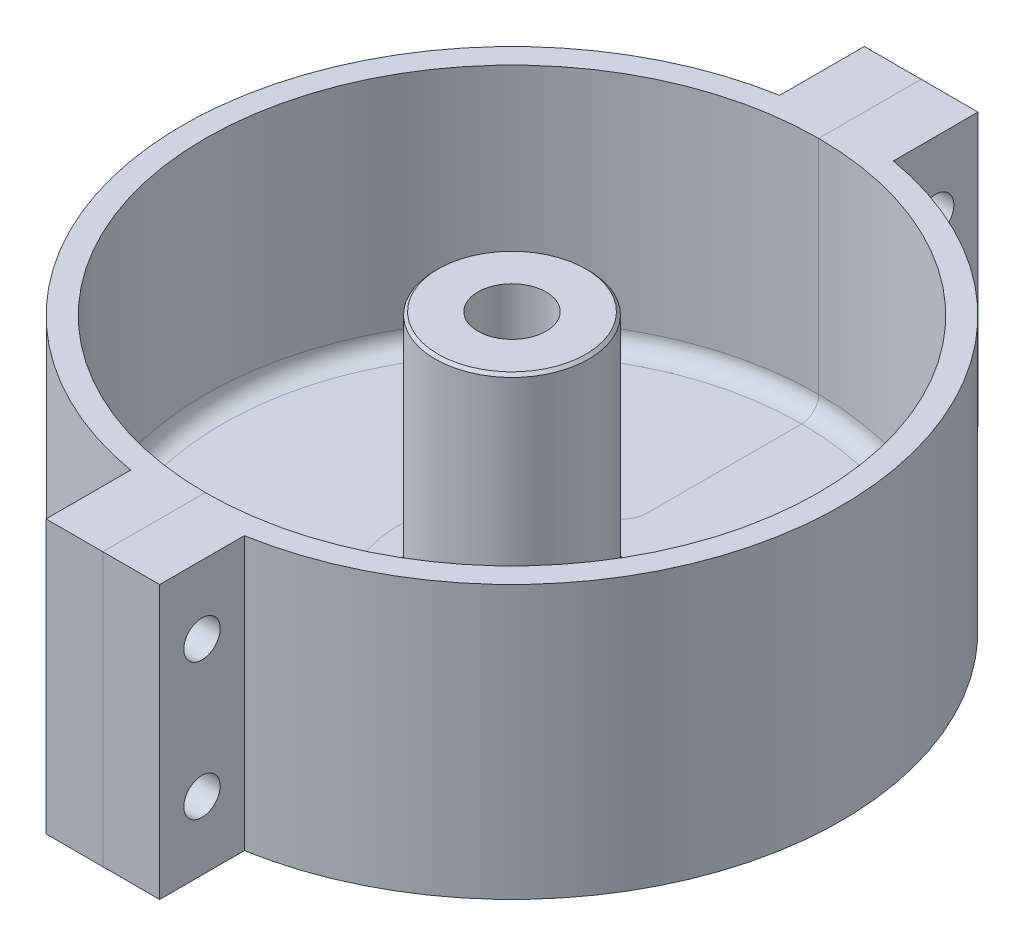
SolidWorks part; units mm, degrees
ref_plane "Front Plane" through (0, 0, 0) normal (0, 0, 1) x (1, 0, 0)
ref_plane "Top Plane" through (0, 0, 0) normal (0, 1, 0) x (1, 0, 0)
ref_plane "Right Plane" through (0, 0, 0) normal (1, 0, 0) x (0, 0, -1)
sketch "Sketch1" plane through (0, 0, 0) normal (0, 1, 0) x (1, 0, 0)
  circle A0 centre (0, 0) radius 26.9875
  circle A1 centre (0, 0) radius 28.9875
  dimension "D1" = 53.975
  dimension "D2" = 2
extrude "Boss-Extrude1" add sketch "Sketch1" along normal blind 24
extrude "Boss-Extrude2" add sketch "Sketch1<2>" along normal blind 3 contours A0 region at (0, 0, 0)
sketch "Sketch1<2>" plane through (0, 0, 0) normal (0, 1, 0) x (1, 0, 0) same geometry as "Sketch1"
fillet "Fillet1" radius 1.5 1 edges at (0, 3, 26.9875)
sketch "Sketch2" plane through (0, 3, 0) normal (0, 1, 0) x (1, 0, 0)
  circle A0 centre (0, 0) radius 6.75
  dimension "D1" = 13.5
extrude "Boss-Extrude3" add sketch "Sketch2" along normal blind 21.3
sketch "Sketch3" plane through (0, 24, 0) normal (0, 1, 0) x (1, 0, 0)
  line L0 (0, 0) -> (0, 45.2463) construction
  line L1 (5, 36) -> (-5, 36)
  line L2 (5, 36) -> (5, 26)
  line L3 (5, 26) -> (-5, 26)
  line L4 (-5, 36) -> (-5, 26)
  circle A0 centre (0, 0) radius 28.9875 construction
  arc A1 (5, 28.553) -> (-5, 28.553) centre (0, 0) ccw
  circle M2 centre (0, 0) radius 28.9875
  dimension "D1" = 10
  dimension "D2" = 26
  dimension "D3" = 10
extrude "Boss-Extrude4" add sketch "Sketch3" against normal up to surface (24 mm away) contours A1 L0 L1 L4 | L0 L2 L1 M2 region at (-2.5253, 24, -32.4204) region at (2.5253, 24, -32.4204) up to face at (0, 0, 28.9875)
hole_wizard "M3 Clearance Hole1" positions "Sketch5" profile "Sketch7" hole size "M3" standard "ANSI Metric" end condition through all
sketch "Sketch5" plane through (-5, 0, 0) normal (-1, 0, 0) x (0, 0, 1)
  line L0 (-36, 24) -> (-28.553, 24) construction
  line L1 (-36, 24) -> (-28.553, 24)
  line L2 (-28.553, 0) -> (-36, 0) construction
  point P0 (-32.2765, 18)
  point P2 (-32.2765, 6)
  point P7 (-32.2765, 24)
  dimension "D1" = 6
  dimension "D2" = 6
sketch "Sketch7" plane through (-5, 18, -32.2765) normal (0, 1, 0) x (0, 0, 1)
  line L0 (0, 0) -> (0, 33.9875)
  line L1 (0, 33.9875) -> (1.6, 33.9875)
  line L2 (1.6, 33.9875) -> (1.6, 0)
  line L5 (1.6, 0) -> (0, 0)
  line L11 (0, -6.35) -> (0, 107.95) construction
  dimension "Thru Hole Dia." = 3.2
  dimension "Thru Hole Depth" = 33.9875
chamfer "Chamfer1" distance 1 angle 45 1 edges at (0, 3, 6.75)
mirror "Mirror1" about plane through (0, 0, 0) normal (0, 0, 1) of "Boss-Extrude4", "M3 Clearance Hole1"
sketch "Sketch8" plane through (0, 24, 0) normal (0, 1, 0) x (1, 0, 0)
  line L0 (0, 36) -> (0, 11.8322)
  line L1 (5, 36) -> (-5, 36) construction
  line L2 (0, -36) -> (0, -11.8322)
  line L3 (5, -36) -> (-5, -36) construction
  arc A0 (-1.6667, 9.8601) -> (-1.6667, -9.8601) centre (0, 0) ccw
  arc A1 (0, -11.8322) -> (-1.6667, -9.8601) centre (-2, -11.8322) ccw
  arc A2 (0, 11.8322) -> (-1.6667, 9.8601) centre (-2, 11.8322) cw
  point P15 (0, 10)
  dimension "D1" = 20
  dimension "D2" = 2
sketch "Sketch9" plane through (0, 24, 0) normal (0, 1, 0) x (1, 0, 0)
  line L0 (26.9735, 0.8701) -> (25.7375, 1)
  line L1 (25.7375, 1) -> (25.7375, -1)
  line L2 (25.7375, -1) -> (26.9735, -0.8701)
  line L3 (0, 0) -> (33.465, 0) construction
  circle A1 centre (0, 0) radius 26.9875 construction
  circle A2 centre (0, 0) radius 26.9875
  circle A3 centre (0, 0) radius 26.9875 construction
  point P6 (26.9875, 0)
  circle M9 centre (0, 0) radius 26.9875
  dimension "D1" = 1.25
  dimension "D2" = 2
  dimension "D3" = 84
extrude "Boss-Extrude5" [suppressed] add sketch "Sketch9" against normal up to surface (21 mm away) contours L3 L1 L2 A2 | L1 L3 L0 M9 up to face at (0, 3, 7.75)
fillet "Fillet2" [suppressed] radius 0.5
pattern_circular "CirPattern1" [suppressed] count 28 over 360 of bodies 109
split "Split1" trim tools "Sketch8" bodies to split 106 resulting bodies 107 108
chamfer "Chamfer3" distance 0.25 angle 45 1 edges at (0, 24.3, 6.75)
hole_wizard "1/4-20 Tapped Hole1" positions "Sketch10" profile "Sketch12" tap size "1/4-20" standard "ANSI Inch" end condition through all
sketch "Sketch10" plane through (0, 24.3, 0) normal (0, 1, 0) x (1, 0, 0)
  point P0 (0, 0)
sketch "Sketch12" plane through (0, 24.3, 0) normal (1, 0, 0) x (0, 0, 1)
  line L0 (0, 0) -> (0, 24.3)
  line L1 (0, 24.3) -> (3, 24.3)
  line L2 (3, 24.3) -> (3, 0)
  line L5 (3, 0) -> (0, 0)
  line L11 (0, -6.35) -> (0, 107.95) construction
  dimension "Thru Tap Drill Dia." = 6
  dimension "Thru Tap Drill Depth" = 24.3
cosmetic thread "Hole Thread1" parameters "D2"=6.35
